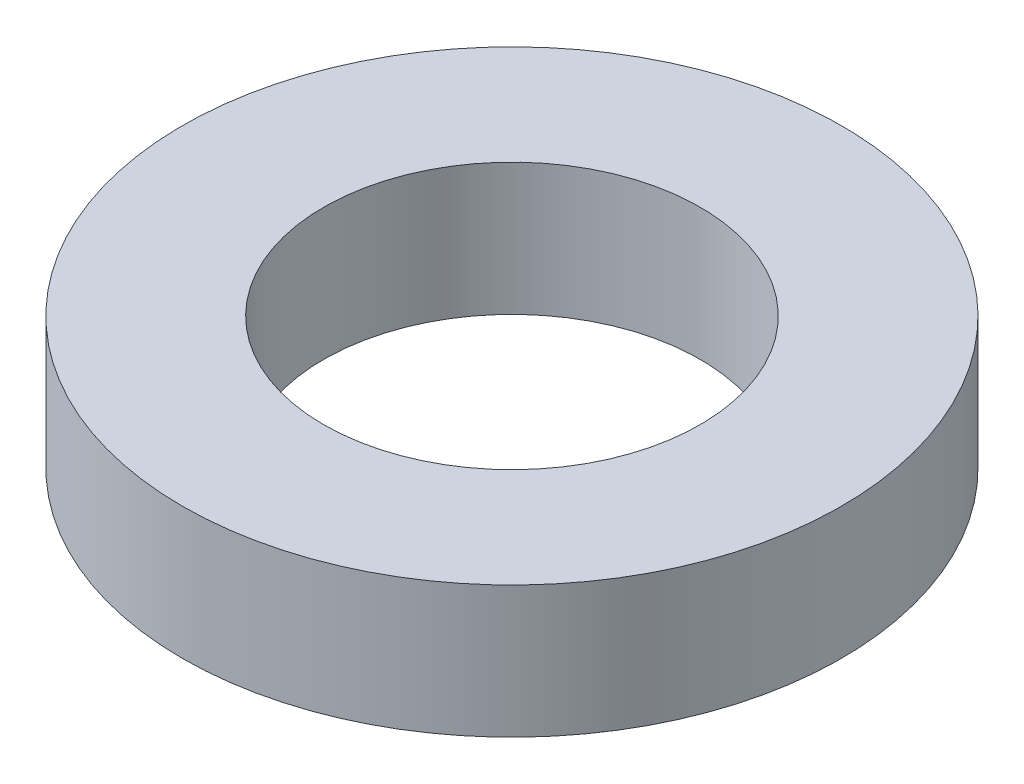
SolidWorks part; units mm, degrees
ref_plane "Front Plane" through (0, 0, 0) normal (0, 0, 1) x (1, 0, 0)
ref_plane "Top Plane" through (0, 0, 0) normal (0, 1, 0) x (1, 0, 0)
ref_plane "Right Plane" through (0, 0, 0) normal (1, 0, 0) x (0, 0, -1)
sketch "Sketch1" plane through (0, 0, 0) normal (0, 1, 0) x (1, 0, 0)
  circle A0 centre (0, 0) radius 35
  dimension "FLANGE_OD" = 70
extrude "Boss-Extrude1" add sketch "Sketch1" along normal blind 14
sketch "Sketch2" plane through (0, 0, 0) normal (0, 1, 0) x (1, 0, 0)
  circle A0 centre (0, 0) radius 20
  dimension "BORE_D" = 40
extrude "Cut-Extrude1" cut sketch "Sketch2" along normal through all
sketch "Sketch3" plane through (0, 14, 0) normal (0, 1, 0) x (1, 0, 0)
  circle A0 centre (0, 0) radius 11.6396 construction
  circle A1 centre (-11.6396, 0) radius 1.9083
  dimension "BOLT_D" = 3.8166
  dimension "BOLT_PCD" = 23.2792
extrude "Cut-Extrude2" cut sketch "Sketch3" against normal blind 13.1273 rebuild error yes
pattern_circular "CirPattern1" count 5 over 360 rebuild error yes
